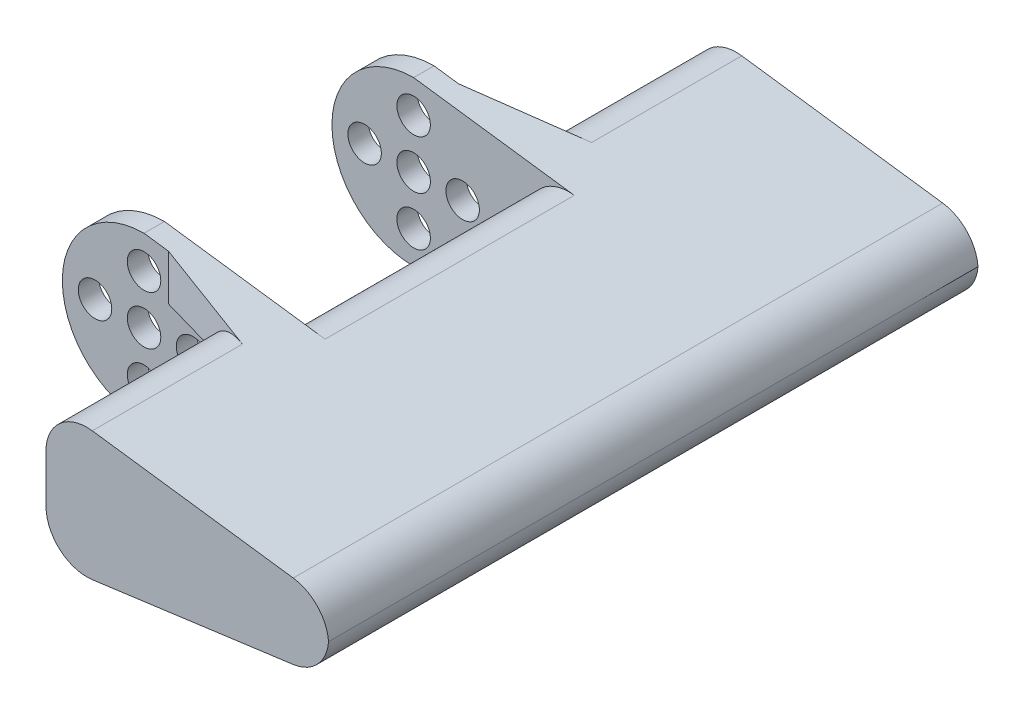
SolidWorks part; units mm, degrees
ref_plane "Face" through (0, 0, 0) normal (0, 0, 1) x (1, 0, 0)
ref_plane "Dessus" through (0, 0, 0) normal (0, 1, 0) x (1, 0, 0)
ref_plane "Droite" through (0, 0, 0) normal (1, 0, 0) x (0, 0, -1)
sketch "Esquisse1" plane through (0, 0, 0) normal (0, 0, 1) x (1, 0, 0)
  line L0 (0, 0) -> (44.5982, 6)
  line L1 (44.5982, 6) -> (44.5982, 14)
  line L2 (44.5982, 14) -> (0, 20)
  line L3 (0, 0) -> (0, 20) construction
  arc A0 (0, 0) -> (0, 20) centre (0, 10) cw
  dimension "D1" = 10
  dimension "D2" = 45
  dimension "D3" = 8
extrude "Boss.-Extru.1" add sketch "Esquisse1" along normal blind 2.5
sketch "Esquisse2" plane through (0, 0, 2.5) normal (0, 0, 1) x (1, 0, 0)
  line L0 (0, 0) -> (0, 20) construction
  line L1 (0, 10) -> (-6, 10) construction
  circle A0 centre (-6, 10) radius 2.05
  circle A1 centre (0, 4) radius 2.05
  circle A2 centre (0, 16) radius 2.05
  circle A3 centre (6, 10) radius 2.05
  circle A4 centre (0, 10) radius 2.05
  dimension "D1" = 4.1
  dimension "D2" = 6
  dimension "D3" = 6
extrude "Enlèv. mat.-Extru.1" cut sketch "Esquisse2" against normal through all
sketch "Esquisse5" plane through (0, 0, 2.5) normal (0, 0, 1) x (1, 0, 0)
  line L0 (44.5982, 14) -> (14, 18.1165)
  line L1 (44.5982, 14) -> (0, 20) construction
  line L2 (14, 18.1165) -> (14, 1.8835)
  line L3 (0, 0) -> (44.5982, 6) construction
  line L4 (14, 1.8835) -> (44.5982, 6)
  line L5 (44.5982, 6) -> (44.5982, 14)
  circle A0 centre (0, 4) radius 2.05 construction
  dimension "D1" = 14
extrude "Boss.-Extru.2" add sketch "Esquisse5" along normal blind 33
sketch "Esquisse6" plane through (0, 0, 35.5) normal (0, 0, 1) x (1, 0, 0)
  line L0 (44.5982, 14) -> (0, 20)
  line L1 (44.5982, 14) -> (44.5982, 6)
  line L2 (44.5982, 6) -> (0, 0)
  line L3 (0, 4) -> (0, 16) construction
  arc A0 (0, 0) -> (0, 20) centre (0, 10) cw
  circle A1 centre (0, 16) radius 2.05
  circle A2 centre (-6, 10) radius 2.05
  circle A3 centre (6, 10) radius 2.05
  circle A4 centre (0, 4) radius 2.05
  circle A5 centre (0, 10) radius 2.05
  dimension "D1" = 4.1
extrude "Boss.-Extru.3" add sketch "Esquisse6" against normal blind 2.5
sketch "Esquisse9" plane through (0, 0, 35.5) normal (0, 0, 1) x (1, 0, 0)
  line L0 (44.5982, 14) -> (3, 19.5964)
  line L2 (44.5982, 10) -> (3.95, 10) construction
  line L3 (0, 0) -> (44.5982, 6) construction
  line L4 (3, 0.4036) -> (44.5982, 6)
  line L5 (44.5982, 6) -> (44.5982, 14)
  line L7 (3, 0.4036) -> (3, 6)
  line L8 (3, 6) -> (10, 6)
  line L9 (10, 6) -> (10, 14)
  line L10 (3, 14) -> (10, 14)
  line L11 (3, 19.5964) -> (3, 14)
  circle A0 centre (6, 10) radius 2.05 construction
  circle A1 centre (0, 4) radius 2.05 construction
  point P22 (10, 10)
  dimension "D1" = 3
  dimension "D2" = 4
  dimension "D3" = 4
extrude "Boss.-Extru.4" add sketch "Esquisse9" along normal blind 2
extrude "Boss.-Extru.5" add sketch "Esquisse9<2>" against normal blind 2 from vertex starting at point (0, 0, 0)
sketch "Esquisse9<2>" plane through (0, 0, 35.5) normal (0, 0, 1) x (1, 0, 0) same geometry as "Esquisse9"
sketch "Esquisse11" plane through (0, 0, 0) normal (0, 1, 0) x (1, 0, 0)
  line L0 (3, -35.5) -> (10, -37.5)
  line L1 (10, -37.5) -> (3, -37.5)
  line L2 (3, -37.5) -> (3, -35.5)
  line L3 (14, -17.75) -> (44.5982, -17.75) construction
  line L4 (14, -33) -> (14, -2.5) construction
  line L5 (44.5982, -37.5) -> (44.5982, 2) construction
  line L6 (3, 2) -> (3, 0)
  line L7 (10, 2) -> (3, 2)
  line L8 (3, 0) -> (10, 2)
extrude "Enlèv. mat.-Extru.5" cut sketch "Esquisse11" against normal through all and the other way through all
sketch "Esquisse12" plane through (0, 0, -2) normal (0, 0, -1) x (-1, 0, 0)
  line L0 (-44.5982, 14) -> (-44.5982, 6)
  line L1 (-44.5982, 6) -> (-10, 1.3453)
  line L2 (-10, 1.3453) -> (-10, 18.6547)
  line L3 (-10, 18.6547) -> (-44.5982, 14)
extrude "Boss.-Extru.6" add sketch "Esquisse12" along normal blind 20
extrude "Boss.-Extru.7" add sketch "Esquisse12<2>" against normal blind 20 from vertex starting at point (44.5982, 6, 37.5)
sketch "Esquisse12<2>" plane through (0, 0, -2) normal (0, 0, -1) x (-1, 0, 0) same geometry as "Esquisse12"
fillet "Congé1" radius 5 8 edges at (10, 18.6547, 47.5) (10, 1.3453, 47.5) (10, 18.6547, -12) (10, 1.3453, -12) (44.5982, 14, 17.75) (44.5982, 6, 17.75)
